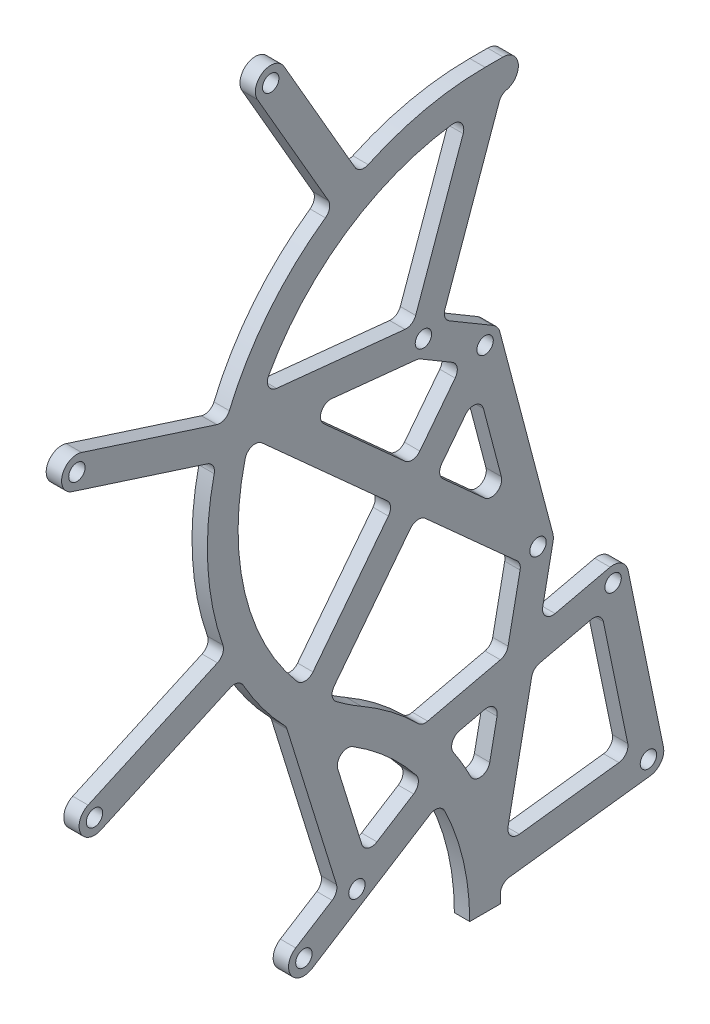
SolidWorks part; units mm, degrees
material "6061 Alloy"
ref_plane "Front Plane" through (0, 0, 0) normal (0, 0, 1) x (1, 0, 0)
ref_plane "Top Plane" through (0, 0, 0) normal (0, 1, 0) x (1, 0, 0)
ref_plane "Right Plane" through (0, 0, 0) normal (1, 0, 0) x (0, 0, -1)
sketch "Sketch1" plane through (0, 0, 0) normal (1, 0, 0) x (0, 0, -1)
  line L0 (0, -35.3347) -> (0, 140) construction
  line L1 (0, 140) -> (67.935, 140) construction
  arc A0 (0, 140) -> (-25.6218, 44.3782) centre (0, 88.7564) ccw
  arc A1 (-25.6218, 44.3782) -> (0, 0) centre (-51.2436, 0) cw
  dimension "D1" = 140
sketch "Sketch2" plane through (0, 0, 0) normal (0, 1, 0) x (1, 0, 0)
  line L0 (0, 0) -> (0, 67.935) construction
  line L1 (0, 3) -> (3, 3)
  line L2 (0, 3) -> (0, -3)
  line L3 (0, -3) -> (3, -3)
  line L4 (3, 3) -> (3, -3)
  dimension "D1" = 3
  dimension "D2" = 6
  dimension "D3" = 3
sweep "Sweep1" add profiles "Sketch2" path "Sketch1"
sketch "Sketch3" plane through (0, 0, 0) normal (-1, 0, 0) x (0, 0, 1)
  line L0 (0, 96) -> (0, 0) construction
  line L1 (-25, 43.3013) -> (0, 0) construction
  line L2 (25.0329, 16.5335) -> (0, 0) construction
  line L3 (51.2436, 0) -> (25.0329, 16.5335) construction
  line L4 (5.3649, 28.9398) -> (10.4397, 25.7387) construction
  line L5 (-3, 0) -> (3, 0) construction
  circle A0 centre (0, 96) radius 1.6
  circle A1 centre (0, 96) radius 3
  circle A2 centre (-25, 43.3013) radius 1.6
  circle A3 centre (25.0329, 16.5335) radius 1.6
  circle A4 centre (-25, 43.3013) radius 3
  circle A5 centre (25.0329, 16.5335) radius 3
  circle A6 centre (35.3905, 10) radius 2.4649 construction
  arc A7 (24.1218, 46.9763) -> (-3, 0) centre (51.2436, 0) ccw construction
  arc A8 (27.1218, 41.7801) -> (3, 0) centre (51.2436, 0) ccw construction
  point P11 (51.2436, 0)
  point P24 (7.9023, 27.3393)
  dimension "D6" = 3.2
  dimension "D7" = 6
  dimension "D1" = 96
  dimension "D2" = 30
  dimension "D3" = 50
  dimension "D4" = 32.5
  dimension "D5" = 30
  dimension "D8" = 10
extrude "Boss-Extrude1" add sketch "Sketch3" against normal blind 3 separate body
sketch "Sketch5" plane through (0, 0, 0) normal (-1, 0, 0) x (0, 0, 1)
  line L0 (0, 137) -> (0, 143) construction
  line L1 (0, 143) -> (-6.5, 143)
  line L2 (0, 143) -> (0, 137)
  line L3 (0, 137) -> (-6.5, 137)
  line L4 (-6.5, 143) -> (-6.5, 137)
  dimension "D1" = 6.5
extrude "Boss-Extrude2" add sketch "Sketch5" against normal blind 3
fillet "Fillet1" radius 3 2 edges at (1.5, 137, -6.5) (1.5, 143, -6.5)
sketch "Sketch6" plane through (0, 0, 0) normal (-1, 0, 0) x (0, 0, 1)
  line L0 (0, 88.7564) -> (65.8774, 167.2661) construction
  line L1 (43.9549, 68.8717) -> (49.4216, 66.3986) construction
  line L2 (-3, 0) -> (3, 0) construction
  line L3 (34.8671, 130.3094) -> (31.0104, 125.7132) construction
  line L4 (27.1218, 135.7327) -> (24.1218, 130.5366) construction
  line L5 (41.8718, 161.2805) -> (79.7216, 114.3972) construction
  line L6 (79.7216, 114.3972) -> (76.2992, 54.2395) construction
  line L7 (76.2992, 54.2395) -> (35.3905, 10) construction
  line L8 (45.9266, 103.5277) -> (51.6384, 105.3648) construction
  line L9 (5.3649, 28.9398) -> (10.4397, 25.7387) construction
  line L10 (23.5, 0) -> (35.5, 0) construction
  line L11 (11.3553, 36.7599) -> (15.7674, 32.6938) construction
  line L12 (-2.6119, 6.4773) -> (3.3452, 5.7609) construction
  line L13 (12.0481, 103.1148) -> (-10.3376, 56.7516) construction
  line L14 (-10.3376, 56.7516) -> (-31.9008, 10) construction
  line L15 (-34.9342, 0) -> (-22.9342, 0) construction
  circle A0 centre (12.0481, 103.1148) radius 1.6
  arc A2 (24.1218, 46.9763) -> (-3, 0) centre (51.2436, 0) ccw construction
  arc A3 (27.1218, 41.7801) -> (0, 143) centre (0, 88.7564) ccw construction
  arc A4 (24.1218, 46.9763) -> (0, 137) centre (0, 88.7564) ccw construction
  circle A5 centre (12.0481, 103.1148) radius 3
  circle A7 centre (41.8718, 161.2805) radius 1.6
  circle A8 centre (41.8718, 161.2805) radius 3
  circle A9 centre (79.7216, 114.3972) radius 1.6
  circle A10 centre (76.2992, 54.2395) radius 1.6
  circle A11 centre (35.3905, 10) radius 1.6
  arc A12 (27.1218, 41.7801) -> (3, 0) centre (51.2436, 0) ccw construction
  circle A13 centre (79.7216, 114.3972) radius 3
  circle A14 centre (76.2992, 54.2395) radius 3
  circle A15 centre (35.3905, 10) radius 3
  circle A16 centre (-10.3376, 56.7516) radius 1.6
  circle A17 centre (-31.9008, 10) radius 1.6
  circle A18 centre (-10.3376, 56.7516) radius 3
  circle A19 centre (-31.9008, 10) radius 3
  point P9 (32.9387, 128.0113)
  point P24 (25.6218, 133.1347)
  point P31 (46.6883, 67.6352)
  point P32 (48.7825, 104.4463)
  point P35 (51.2436, 0)
  point P36 (7.9023, 27.3393)
  point P60 (0.3667, 6.1191)
  point P61 (13.5614, 34.7269)
  dimension "D2" = 3.2
  dimension "D4" = 3.2
  dimension "D5" = 6
  dimension "D6" = 6
  dimension "D12" = 3.2
  dimension "D1" = 50
  dimension "D3" = 32.5
  dimension "D7" = 32.5
  dimension "D8" = 60
  dimension "D9" = 32.5
  dimension "D10" = 32.5
  dimension "D11" = 32.5
  dimension "D13" = 10
  dimension "D14" = 32.5
  dimension "D15" = 32.5
  dimension "D16" = 10
extrude "Boss-Extrude3" add sketch "Sketch6" against normal blind 3 separate body
sketch "Sketch7" plane through (0, 0, 0) normal (-1, 0, 0) x (0, 0, 1)
  line L0 (0, 88.7564) -> (41.8718, 161.2805) construction
  line L1 (0, 88.7564) -> (79.7216, 114.3972) construction
  line L2 (0, 88.7564) -> (76.2992, 54.2395) construction
  line L3 (51.2436, 0) -> (35.3905, 10) construction
  line L4 (51.2436, 0) -> (-25, 43.3013) construction
  line L5 (51.2436, 0) -> (-31.9008, 10) construction
  line L6 (51.2436, 0) -> (-10.3376, 56.7516) construction
  line L7 (39.2737, 162.7805) -> (24.4822, 137.1608)
  line L8 (44.4699, 159.7805) -> (29.6783, 134.1608)
  line L9 (78.8031, 117.2531) -> (50.6408, 108.1953)
  line L10 (80.6402, 111.5412) -> (52.4779, 102.4835)
  line L11 (77.5357, 56.9728) -> (50.5825, 69.1662)
  line L12 (75.0627, 51.5062) -> (48.1094, 63.6995)
  line L13 (26.6334, 19.0708) -> (36.991, 12.5374)
  line L14 (8.9181, 23.1516) -> (33.7899, 7.4626)
  line L15 (25.0329, 16.5335) -> (51.2436, 0) construction
  line L16 (26.6334, 19.0708) -> (12.1192, 28.2263)
  circle A0 centre (41.8718, 161.2805) radius 3 construction
  arc A1 (27.1218, 41.7801) -> (0, 143) centre (0, 88.7564) ccw construction
  arc A2 (39.2737, 162.7805) -> (44.4699, 159.7805) centre (41.8718, 161.2805) ccw
  arc A3 (24.4822, 137.1608) -> (29.6783, 134.1608) centre (0, 88.7564) cw
  circle A4 centre (79.7216, 114.3972) radius 3 construction
  arc A5 (50.6408, 108.1953) -> (52.4779, 102.4835) centre (0, 88.7564) cw
  arc A6 (78.8031, 117.2531) -> (80.6402, 111.5412) centre (79.7216, 114.3972) ccw
  circle A7 centre (76.2992, 54.2395) radius 3 construction
  arc A8 (50.5825, 69.1662) -> (48.1094, 63.6995) centre (0, 88.7564) cw
  arc A9 (77.5357, 56.9728) -> (75.0627, 51.5062) centre (76.2992, 54.2395) ccw
  circle A10 centre (25.0329, 16.5335) radius 3 construction
  circle A11 centre (35.3905, 10) radius 3 construction
  arc A12 (27.1218, 41.7801) -> (3, 0) centre (51.2436, 0) ccw construction
  arc A13 (12.1192, 28.2263) -> (8.9181, 23.1516) centre (51.2436, 0) ccw
  arc A14 (36.991, 12.5374) -> (33.7899, 7.4626) centre (35.3905, 10) ccw
  circle A16 centre (25.0329, 16.5335) radius 1.6 construction
  circle A17 centre (25.0329, 16.5335) radius 1.6
  point P0 (0, 88.7564)
  point P1 (51.2436, 0)
extrude "Boss-Extrude4" add sketch "Sketch7" against normal blind 3
fillet "Fillet2" radius 2 8 edges at (1.5, 28.2263, 12.1192) (1.5, 23.1516, 8.9181) (1.5, 63.6995, 48.1094) (1.5, 69.1662, 50.5825) (1.5, 102.4835, 52.4779) (1.5, 108.1953, 50.6408) (1.5, 134.1608, 29.6783) (1.5, 137.1608, 24.4822)
sketch "Sketch8" plane through (0, 0, 0) normal (-1, 0, 0) x (0, 0, 1)
  line L0 (0, 96) -> (0, 137) construction
  line L1 (0, 96) -> (-10.3376, 56.7516) construction
  line L2 (0, 96) -> (32.9424, 53.511) construction
  line L3 (-25, 43.3013) -> (-31.9008, 10) construction
  line L4 (-31.9008, 10) -> (-2.6202, 6.4075) construction
  line L5 (-10.3376, 56.7516) -> (44.8765, 106.4635) construction
  line L6 (44.8765, 106.4635) -> (12.0481, 103.1148) construction
  line L7 (-25, 43.3013) -> (9.9813, 35.2107) construction
  line L8 (-10.3376, 56.7516) -> (-1.4989, 12.6727) construction
  line L9 (-25, 43.3013) -> (-10.3376, 56.7516) construction
  line L10 (0, 96) -> (12.0481, 103.1148) construction
  line L11 (12.0481, 103.1148) -> (0, 137) construction
  line L15 (12.0481, 103.1148) -> (0, 137) construction
  line L16 (8.3931, 104.4404) -> (-3.1837, 137)
  line L17 (14.0858, 106.3383) -> (3.222, 136.8923)
  line L18 (0, 96) -> (12.0481, 103.1148) construction
  line L19 (-1.5255, 98.5832) -> (8.3931, 104.4404)
  line L21 (12.0481, 103.1148) -> (44.8765, 106.4635) construction
  line L22 (14.0858, 106.3383) -> (43.6266, 109.3515)
  line L23 (13.0071, 100.1971) -> (36.0428, 102.5468)
  line L24 (44.8765, 106.4635) -> (-10.3376, 56.7516) construction
  line L25 (45.9653, 103.4069) -> (17.7495, 78.0029)
  line L26 (36.0428, 102.5468) -> (14.0632, 82.7575)
  line L27 (-10.3376, 56.7516) -> (0, 96) construction
  line L28 (-13.209, 57.6205) -> (-2.8714, 96.869)
  line L30 (0, 96) -> (32.9424, 53.511) construction
  line L33 (-10.3376, 56.7516) -> (-1.4989, 12.6727) construction
  line L34 (-7.0602, 55.6656) -> (-4.2353, 41.5779)
  line L35 (-13.2791, 56.1617) -> (-10.6523, 43.0621)
  line L36 (-3.5, 137) -> (0, 137) construction
  line L39 (-25, 43.3013) -> (9.9813, 35.2107) construction
  line L40 (-24.4125, 46.2446) -> (-10.6523, 43.0621)
  line L42 (-25, 43.3013) -> (-31.9008, 10) construction
  line L43 (-22.0624, 42.6925) -> (-22.0764, 42.6251)
  line L44 (-27.9376, 43.91) -> (-34.8384, 10.6087)
  line L45 (-31.9008, 10) -> (-2.6202, 6.4075) construction
  line L46 (-28.3022, 12.581) -> (-3.9409, 9.592)
  line L47 (-32.2661, 7.0223) -> (-2.8922, 3.4183)
  line L48 (-4.2353, 41.5779) -> (12.2955, 37.7547)
  line L49 (-9.3574, 36.6042) -> (-3.9409, 9.592)
  line L51 (-3.1837, 137) -> (0, 137)
  line L52 (0, 137) -> (44.8765, 106.4635) construction
  line L53 (-2.9404, 35.1201) -> (0.3427, 18.7474)
  line L54 (4.4568, 95.1478) -> (14.0632, 82.7575)
  line L55 (-4.8772, 65.7047) -> (1.3531, 89.3587)
  line L56 (44.8765, 106.4635) -> (32.9424, 53.511) construction
  line L57 (4.4568, 95.1478) -> (13.0071, 100.1971)
  line L58 (1.3531, 89.3587) -> (9.5921, 78.732)
  line L59 (9.5921, 78.732) -> (-4.8772, 65.7047)
  line L60 (17.7495, 78.0029) -> (35.0852, 55.6434)
  line L61 (13.2784, 73.9774) -> (-7.0602, 55.6656)
  line L62 (13.2784, 73.9774) -> (30.6837, 51.5281)
  line L63 (-2.9404, 35.1201) -> (7.899, 32.6131)
  line L64 (-22.6856, 39.6851) -> (-28.3022, 12.581)
  line L65 (-22.6856, 39.6851) -> (-9.3574, 36.6042)
  line L66 (32.9424, 53.511) -> (9.9813, 35.2107) construction
  line L67 (9.9813, 35.2107) -> (-2.6202, 6.4075) construction
  arc A0 (24.1218, 46.9763) -> (-3, 0) centre (51.2436, 0) ccw construction
  circle A1 centre (-31.9008, 10) radius 1.6 construction
  arc A2 (24.1218, 46.9763) -> (0, 137) centre (0, 88.7564) ccw construction
  arc A12 (-13.209, 57.6205) -> (-13.2791, 56.1617) centre (-10.3376, 56.7516) ccw
  arc A13 (-13.209, 57.6205) -> (-13.2791, 56.1617) centre (-10.3376, 56.7516) ccw
  circle A27 centre (-25, 43.3013) radius 1.6 construction
  circle A28 centre (-10.3376, 56.7516) radius 1.6 construction
  circle A29 centre (0, 96) radius 1.6 construction
  circle A30 centre (12.0481, 103.1148) radius 1.6 construction
  circle A31 centre (-31.9008, 10) radius 1.6
  circle A32 centre (-25, 43.3013) radius 1.6
  circle A33 centre (-10.3376, 56.7516) radius 1.6
  circle A34 centre (0, 96) radius 1.6
  circle A35 centre (12.0481, 103.1148) radius 1.6
  arc A39 (-13.209, 57.6205) -> (-13.2791, 56.1617) centre (-10.3376, 56.7516) ccw
  circle A40 centre (0, 96) radius 3 construction
  circle A41 centre (-31.9008, 10) radius 3 construction
  circle A42 centre (-25, 43.3013) radius 3 construction
  arc A43 (43.6266, 109.3515) -> (45.9653, 103.4069) centre (0, 88.7564) cw
  arc A44 (0, 137) -> (3.222, 136.8923) centre (0, 88.7564) cw
  arc A45 (-1.5255, 98.5832) -> (-2.8714, 96.869) centre (0, 96) ccw
  circle A46 centre (-10.3376, 56.7516) radius 3 construction
  arc A47 (-24.4125, 46.2446) -> (-27.9376, 43.91) centre (-24.9986, 43.301) ccw
  arc A48 (-34.8384, 10.6087) -> (-32.2661, 7.0223) centre (-31.9008, 10) ccw
  arc A49 (0.3427, 18.7474) -> (-2.8922, 3.4183) centre (51.2436, 0) ccw
  arc A50 (7.899, 32.6131) -> (12.2955, 37.7547) centre (51.2436, 0) cw
  arc A51 (35.0852, 55.6434) -> (30.6837, 51.5281) centre (0, 88.7564) cw
  point P31 (6.0241, 120.0574)
  point P39 (6.0241, 99.5574)
  point P44 (29.5495, 101.2663)
  point P50 (18.3566, 78.0847)
  point P56 (-5.1688, 76.3758)
  point P64 (18.0494, 76.3758)
  point P70 (-5.9183, 34.7121)
  point P83 (-7.1339, 39.6867)
  point P89 (-28.4504, 26.6506)
  point P95 (-17.2563, 8.2387)
  dimension "D1" = 3
  dimension "D4" = 3
  dimension "D2" = 2.9998
  dimension "D3" = 2.9998
  dimension "D5" = 3
  dimension "D6" = 3
  dimension "D7" = 2.998
  dimension "D8" = 3
  dimension "D9" = 3
  dimension "D10" = 3
  dimension "D11" = 3
  dimension "D12" = 3
  dimension "D13" = 3
  dimension "D14" = 3
  dimension "D15" = 3
  dimension "D16" = 3
  dimension "D17" = 3
extrude "Boss-Extrude7" add sketch "Sketch8" against normal blind 3 contours L63 A50 L48 L34 L61 L62 L60 L25 L22 L17 L16 L19 A45 L28 A12 L35 L40 A47 L44 A48 L47 A49 L53 L64 L65 L49 L46 L58 L59 L55 L54 L57 L23 L26 A31 A32 A33 region at (0, 66.3413, 2.8579)
fillet "Fillet3" radius 2 29 edges at (1.5, 43.0621, -10.6523) (1.5, 12.581, -28.3022) (1.5, 9.592, -3.9409) (1.5, 3.4183, -2.8922) (1.5, 39.6851, -22.6856) (1.5, 36.6042, -9.3574) (1.5, 35.1201, -2.9404) (1.5, 32.6131, 7.899) (1.5, 18.7474, 0.3427) (1.5, 41.5779, -4.2353) (1.5, 37.7547, 12.2955) (1.5, 55.6434, 35.0852) (1.5, 51.5281, 30.6837) (1.5, 55.6656, -7.0602) (1.5, 78.0029, 17.7495) (1.5, 73.9774, 13.2784) (1.5, 103.4069, 45.9653) (1.5, 78.732, 9.5921) (1.5, 89.3587, 1.3531) (1.5, 65.7047, -4.8772) (1.5, 82.7575, 14.0632) (1.5, 100.1971, 13.0071) (1.5, 95.1478, 4.4568) (1.5, 102.5468, 36.0428) (1.5, 104.4404, 8.3931) (1.5, 109.3515, 43.6266) (1.5, 106.3383, 14.0858) (1.5, 136.8923, 3.222) (1.5, 137, -3.1837)
sketch "Sketch10" plane through (0, 0, 0) normal (-1, 0, 0) x (0, 0, 1)
  line L0 (22.1677, 17.4228) -> (30.3552, 43.8018)
  line L1 (27.898, 15.6442) -> (38.8369, 50.8875)
  line L2 (36.991, 12.5374) -> (13.9611, 27.0644) construction
  circle A0 centre (25.0329, 16.5335) radius 3
  arc A1 (27.1218, 41.7801) -> (47.2383, 62.0936) centre (0, 88.7564) ccw construction
  arc A2 (30.3552, 43.8018) -> (38.8369, 50.8875) centre (0, 88.7564) ccw
  dimension "D1" = 6
  dimension "D2" = 75
extrude "Boss-Extrude8" add sketch "Sketch10" against normal blind 3 contours A2 L0 A0 L1 region at (0, 32.9599, 30.2945)
fillet "Fillet4" radius 2 4 edges at (1.5, 43.8018, 30.3552) (1.5, 50.8875, 38.8369) (1.5, 17.8427, 28.5804) (1.5, 21.1567, 23.3266)
